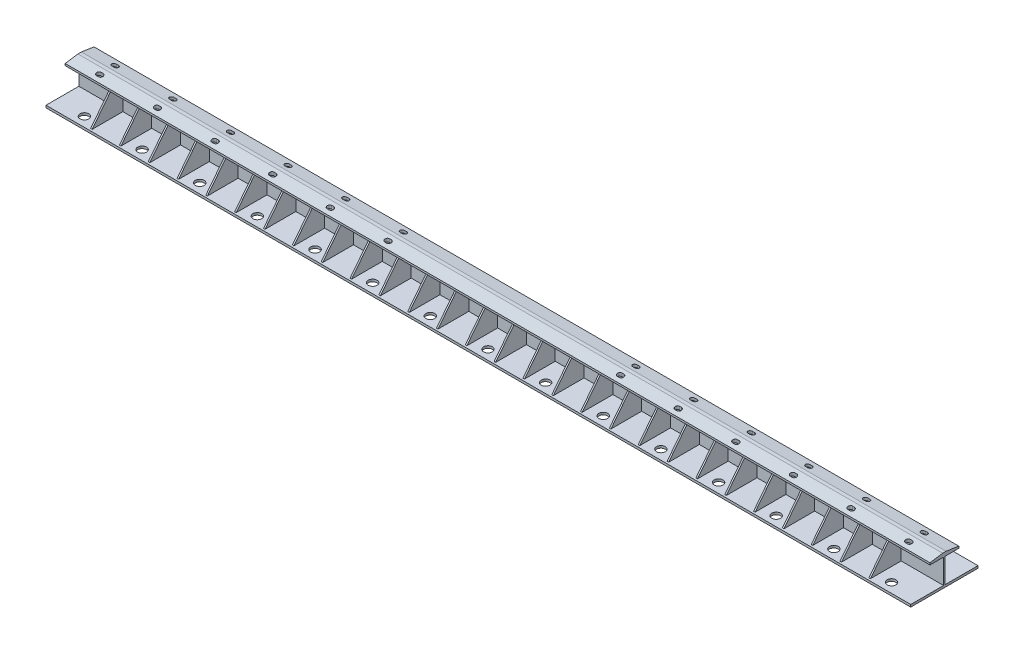
SolidWorks part; units mm, degrees
ref_plane "前视基准面" through (0, 0, 0) normal (0, 0, 1) x (1, 0, 0)
ref_plane "上视基准面" through (0, 0, 0) normal (0, 1, 0) x (1, 0, 0)
ref_plane "右视基准面" through (0, 0, 0) normal (1, 0, 0) x (0, 0, -1)
sketch "草图1" plane through (0, 0, 0) normal (0, 1, 0) x (1, 0, 0)
  line L1 (-2250, 75) -> (2250, 75)
  line L2 (-2250, 75) -> (-2250, -75)
  line L3 (-2250, -75) -> (2250, -75)
  line L4 (2250, 75) -> (2250, -75)
  line L5 (-2250, 75) -> (2250, -75) construction
  line L6 (-2250, -75) -> (2250, 75) construction
  line L24 (0, -75) -> (0, 75) construction
  line L25 (2250, 0) -> (-2250, 0) construction
extrude "凸台-拉伸1" add sketch "草图1" along normal blind 20
sketch "草图2" plane through (0, 0, 0) normal (0, -1, 0) x (1, 0, 0)
  line L0 (221, 64) -> (229, 64)
  line L1 (-2250, 4) -> (2250, 4)
  line L2 (-2250, 4) -> (-2250, -4)
  line L3 (-2250, -4) -> (2250, -4)
  line L4 (2250, 4) -> (2250, -4)
  line L5 (-2250, 4) -> (2250, -4) construction
  line L6 (-2250, -4) -> (2250, 4) construction
  line L7 (81.413, 64) -> (89.413, 64)
  line L8 (81.413, 64) -> (81.413, -64)
  line L9 (81.413, -64) -> (89.413, -64)
  line L10 (89.413, 64) -> (89.413, -64)
  line L11 (81.413, 64) -> (89.413, -64) construction
  line L12 (81.413, -64) -> (89.413, 64) construction
  line L13 (221, 64) -> (221, -64)
  line L14 (221, -64) -> (229, -64)
  line L15 (229, 64) -> (229, -64)
  line L16 (221, 64) -> (229, -64) construction
  line L17 (221, -64) -> (229, 64) construction
  line L18 (371, 64) -> (379, 64)
  line L19 (371, 64) -> (371, -64)
  line L20 (371, -64) -> (379, -64)
  line L21 (379, 64) -> (379, -64)
  line L22 (371, 64) -> (379, -64) construction
  line L23 (371, -64) -> (379, 64) construction
  line L24 (521, 64) -> (529, 64)
  line L25 (521, 64) -> (521, -64)
  line L26 (521, -64) -> (529, -64)
  line L27 (529, 64) -> (529, -64)
  line L28 (521, 64) -> (529, -64) construction
  line L29 (521, -64) -> (529, 64) construction
  line L30 (821, 64) -> (829, 64)
  line L31 (821, 64) -> (821, -64)
  line L32 (821, -64) -> (829, -64)
  line L33 (829, 64) -> (829, -64)
  line L34 (821, 64) -> (829, -64) construction
  line L35 (821, -64) -> (829, 64) construction
  line L36 (971, 64) -> (979, 64)
  line L37 (971, 64) -> (971, -64)
  line L38 (971, -64) -> (979, -64)
  line L39 (979, 64) -> (979, -64)
  line L40 (971, 64) -> (979, -64) construction
  line L41 (971, -64) -> (979, 64) construction
  line L42 (1121, 64) -> (1129, 64)
  line L43 (1121, 64) -> (1121, -64)
  line L44 (1121, -64) -> (1129, -64)
  line L45 (1129, 64) -> (1129, -64)
  line L46 (1121, 64) -> (1129, -64) construction
  line L47 (1121, -64) -> (1129, 64) construction
  line L48 (1271, 64) -> (1279, 64)
  line L49 (1271, 64) -> (1271, -64)
  line L50 (1271, -64) -> (1279, -64)
  line L51 (1279, 64) -> (1279, -64)
  line L52 (1271, 64) -> (1279, -64) construction
  line L53 (1271, -64) -> (1279, 64) construction
  line L54 (1571, 64) -> (1579, 64)
  line L55 (1571, 64) -> (1571, -64)
  line L56 (1571, -64) -> (1579, -64)
  line L57 (1579, 64) -> (1579, -64)
  line L58 (1571, 64) -> (1579, -64) construction
  line L59 (1571, -64) -> (1579, 64) construction
  line L60 (1721, 64) -> (1729, 64)
  line L61 (1721, 64) -> (1721, -64)
  line L62 (1721, -64) -> (1729, -64)
  line L63 (1729, 64) -> (1729, -64)
  line L64 (1721, 64) -> (1729, -64) construction
  line L65 (1721, -64) -> (1729, 64) construction
  line L66 (1871, 64) -> (1879, 64)
  line L67 (1871, 64) -> (1871, -64)
  line L68 (1871, -64) -> (1879, -64)
  line L69 (1879, 64) -> (1879, -64)
  line L70 (1871, 64) -> (1879, -64) construction
  line L71 (1871, -64) -> (1879, 64) construction
  line L72 (1421, 64) -> (1429, 64)
  line L73 (1421, 64) -> (1421, -64)
  line L74 (1421, -64) -> (1429, -64)
  line L75 (1429, 64) -> (1429, -64)
  line L76 (1421, 64) -> (1429, -64) construction
  line L77 (1421, -64) -> (1429, 64) construction
  line L78 (671, 64) -> (679, 64)
  line L79 (671, 64) -> (671, -64)
  line L80 (671, -64) -> (679, -64)
  line L81 (679, 64) -> (679, -64)
  line L82 (671, 64) -> (679, -64) construction
  line L83 (671, -64) -> (679, 64) construction
  line L84 (0, 75) -> (0, -75) construction
  line L85 (-2250, 75) -> (2250, 75) construction
  line L86 (2021, 64) -> (2029, 64)
  line L87 (2250, -75) -> (-2250, -75) construction
  line L88 (-2046, -64) -> (-2054, 64) construction
  line L89 (-2046, 64) -> (-2054, -64) construction
  line L90 (2046, 64) -> (2054, 64)
  line L91 (2046, 64) -> (2046, -64)
  line L92 (2046, -64) -> (2054, -64)
  line L93 (2054, 64) -> (2054, -64)
  line L94 (2046, 64) -> (2054, -64) construction
  line L95 (2046, -64) -> (2054, 64) construction
  line L96 (-671, -64) -> (-679, 64) construction
  line L97 (-671, 64) -> (-679, -64) construction
  line L98 (-1421, -64) -> (-1429, 64) construction
  line L99 (-1421, 64) -> (-1429, -64) construction
  line L100 (-1871, -64) -> (-1879, 64) construction
  line L101 (-1871, 64) -> (-1879, -64) construction
  line L102 (-1721, -64) -> (-1729, 64) construction
  line L103 (-1721, 64) -> (-1729, -64) construction
  line L104 (-1571, -64) -> (-1579, 64) construction
  line L105 (-1571, 64) -> (-1579, -64) construction
  line L106 (-1271, -64) -> (-1279, 64) construction
  line L107 (-1271, 64) -> (-1279, -64) construction
  line L108 (-1121, -64) -> (-1129, 64) construction
  line L109 (-1121, 64) -> (-1129, -64) construction
  line L110 (-971, -64) -> (-979, 64) construction
  line L111 (-971, 64) -> (-979, -64) construction
  line L112 (-821, -64) -> (-829, 64) construction
  line L113 (-821, 64) -> (-829, -64) construction
  line L114 (-521, -64) -> (-529, 64) construction
  line L115 (-521, 64) -> (-529, -64) construction
  line L116 (-371, -64) -> (-379, 64) construction
  line L117 (-371, 64) -> (-379, -64) construction
  line L118 (-221, -64) -> (-229, 64) construction
  line L119 (-221, 64) -> (-229, -64) construction
  line L120 (-81.413, -64) -> (-89.413, 64) construction
  line L121 (-81.413, 64) -> (-89.413, -64) construction
  line L122 (-2054, 64) -> (-2054, -64)
  line L123 (-2046, -64) -> (-2054, -64)
  line L124 (-2046, 64) -> (-2046, -64)
  line L125 (-2046, 64) -> (-2054, 64)
  line L126 (-679, 64) -> (-679, -64)
  line L127 (-671, -64) -> (-679, -64)
  line L128 (-671, 64) -> (-671, -64)
  line L129 (-671, 64) -> (-679, 64)
  line L130 (-1429, 64) -> (-1429, -64)
  line L131 (-1421, -64) -> (-1429, -64)
  line L132 (-1421, 64) -> (-1421, -64)
  line L133 (-1421, 64) -> (-1429, 64)
  line L134 (-1879, 64) -> (-1879, -64)
  line L135 (-1871, -64) -> (-1879, -64)
  line L136 (-1871, 64) -> (-1871, -64)
  line L137 (-1871, 64) -> (-1879, 64)
  line L138 (-1729, 64) -> (-1729, -64)
  line L139 (-1721, -64) -> (-1729, -64)
  line L140 (-1721, 64) -> (-1721, -64)
  line L141 (-1721, 64) -> (-1729, 64)
  line L142 (-1579, 64) -> (-1579, -64)
  line L143 (-1571, -64) -> (-1579, -64)
  line L144 (-1571, 64) -> (-1571, -64)
  line L145 (-1571, 64) -> (-1579, 64)
  line L146 (-1279, 64) -> (-1279, -64)
  line L147 (-1271, -64) -> (-1279, -64)
  line L148 (-1271, 64) -> (-1271, -64)
  line L149 (-1271, 64) -> (-1279, 64)
  line L150 (-1129, 64) -> (-1129, -64)
  line L151 (-1121, -64) -> (-1129, -64)
  line L152 (-1121, 64) -> (-1121, -64)
  line L153 (-1121, 64) -> (-1129, 64)
  line L154 (-979, 64) -> (-979, -64)
  line L155 (-971, -64) -> (-979, -64)
  line L156 (-971, 64) -> (-971, -64)
  line L157 (-971, 64) -> (-979, 64)
  line L158 (-829, 64) -> (-829, -64)
  line L159 (-821, -64) -> (-829, -64)
  line L160 (-821, 64) -> (-821, -64)
  line L161 (-821, 64) -> (-829, 64)
  line L162 (-529, 64) -> (-529, -64)
  line L163 (-521, -64) -> (-529, -64)
  line L164 (-521, 64) -> (-521, -64)
  line L165 (-521, 64) -> (-529, 64)
  line L166 (-379, 64) -> (-379, -64)
  line L167 (-371, -64) -> (-379, -64)
  line L168 (-371, 64) -> (-371, -64)
  line L169 (-371, 64) -> (-379, 64)
  line L170 (-229, 64) -> (-229, -64)
  line L171 (-221, -64) -> (-229, -64)
  line L172 (-221, 64) -> (-221, -64)
  line L173 (-89.413, 64) -> (-89.413, -64)
  line L174 (-81.413, -64) -> (-89.413, -64)
  line L175 (-81.413, 64) -> (-81.413, -64)
  line L176 (-81.413, 64) -> (-89.413, 64)
  line L177 (-221, 64) -> (-229, 64)
  line L178 (2021, 64) -> (2021, -64)
  line L179 (2021, -64) -> (2029, -64)
  line L180 (2029, 64) -> (2029, -64)
  line L181 (2021, 64) -> (2029, -64) construction
  line L182 (2021, -64) -> (2029, 64) construction
  line L183 (71, 64) -> (79, 64)
  line L184 (71, 64) -> (71, -64)
  line L185 (71, -64) -> (79, -64)
  line L186 (79, 64) -> (79, -64)
  line L187 (71, 64) -> (79, -64) construction
  line L188 (71, -64) -> (79, 64) construction
  line L189 (-79, 64) -> (-71, 64)
  line L190 (-79, 64) -> (-79, -64)
  line L191 (-79, -64) -> (-71, -64)
  line L192 (-71, 64) -> (-71, -64)
  line L193 (-79, 64) -> (-71, -64) construction
  line L194 (-79, -64) -> (-71, 64) construction
  line L195 (-2029, 64) -> (-2021, 64)
  line L196 (-2029, 64) -> (-2029, -64)
  line L197 (-2029, -64) -> (-2021, -64)
  line L198 (-2021, 64) -> (-2021, -64)
  line L199 (-2029, 64) -> (-2021, -64) construction
  line L200 (-2029, -64) -> (-2021, 64) construction
  point P0 (0, 0)
  point P5 (85.413, 0)
  point P10 (225, 0)
  point P15 (375, 0)
  point P20 (525, 0)
  point P25 (825, 0)
  point P30 (975, 0)
  point P35 (1125, 0)
  point P40 (1275, 0)
  point P45 (1575, 0)
  point P50 (1725, 0)
  point P55 (1875, 0)
  point P60 (1425, 0)
  point P65 (675, 0)
  point P75 (2050, 0)
  point P138 (-2050, 0)
  point P139 (-675, 0)
  point P140 (-1425, 0)
  point P141 (-1875, 0)
  point P142 (-1725, 0)
  point P143 (-1575, 0)
  point P144 (-1275, 0)
  point P145 (-1125, 0)
  point P146 (-975, 0)
  point P147 (-825, 0)
  point P148 (-525, 0)
  point P149 (-375, 0)
  point P150 (-225, 0)
  point P151 (-85.413, 0)
  point P152 (2025, 0)
  point P157 (75, 0)
  point P162 (-75, 0)
  point P167 (-2025, 0)
  dimension "D1" = 8
  dimension "D2" = 128
sketch "草图3" plane through (0, 0, 0) normal (0, -1, 0) x (1, 0, 0)
  line L0 (-610, 40) -> (-600, 40) construction
  line L1 (-610, 52) -> (-600, 52)
  line L2 (-610, 28) -> (-600, 28)
  line L3 (-910, 40) -> (-900, 40) construction
  line L4 (-910, 52) -> (-900, 52)
  line L5 (-910, 28) -> (-900, 28)
  line L6 (-1210, 40) -> (-1200, 40) construction
  line L7 (-1210, 52) -> (-1200, 52)
  line L8 (-1210, 28) -> (-1200, 28)
  line L9 (-1510, 40) -> (-1500, 40) construction
  line L10 (-1510, 52) -> (-1500, 52)
  line L11 (-1510, 28) -> (-1500, 28)
  line L12 (-1810, 40) -> (-1800, 40) construction
  line L13 (-1810, 52) -> (-1800, 52)
  line L14 (-1810, 28) -> (-1800, 28)
  line L15 (-2110, 40) -> (-2100, 40) construction
  line L16 (-2110, 52) -> (-2100, 52)
  line L17 (-2110, 28) -> (-2100, 28)
  line L18 (-2110, -40) -> (-2100, -40) construction
  line L19 (-2110, -28) -> (-2100, -28)
  line L20 (-2110, -52) -> (-2100, -52)
  line L21 (-1810, -40) -> (-1800, -40) construction
  line L22 (-1810, -28) -> (-1800, -28)
  line L23 (-1810, -52) -> (-1800, -52)
  line L24 (-1510, -40) -> (-1500, -40) construction
  line L25 (-1510, -28) -> (-1500, -28)
  line L26 (-1510, -52) -> (-1500, -52)
  line L27 (-1210, -40) -> (-1200, -40) construction
  line L28 (-1210, -28) -> (-1200, -28)
  line L29 (-1210, -52) -> (-1200, -52)
  line L30 (-910, -40) -> (-900, -40) construction
  line L31 (-910, -28) -> (-900, -28)
  line L32 (-910, -52) -> (-900, -52)
  line L33 (600, -40) -> (610, -40) construction
  line L34 (600, -28) -> (610, -28)
  line L35 (600, -52) -> (610, -52)
  line L36 (600, 40) -> (610, 40) construction
  line L37 (600, 52) -> (610, 52)
  line L38 (600, 28) -> (610, 28)
  line L39 (-610, -40) -> (-600, -40) construction
  line L40 (-610, -28) -> (-600, -28)
  line L41 (-610, -52) -> (-600, -52)
  line L42 (900, 40) -> (910, 40) construction
  line L43 (900, 52) -> (910, 52)
  line L44 (900, 28) -> (910, 28)
  line L45 (900, -40) -> (910, -40) construction
  line L46 (900, -28) -> (910, -28)
  line L47 (900, -52) -> (910, -52)
  line L48 (1200, 40) -> (1210, 40) construction
  line L49 (1200, 52) -> (1210, 52)
  line L50 (1200, 28) -> (1210, 28)
  line L51 (1200, -40) -> (1210, -40) construction
  line L52 (1200, -28) -> (1210, -28)
  line L53 (1200, -52) -> (1210, -52)
  line L54 (1500, 40) -> (1510, 40) construction
  line L55 (1500, 52) -> (1510, 52)
  line L56 (1500, 28) -> (1510, 28)
  line L57 (1500, -40) -> (1510, -40) construction
  line L58 (1500, -28) -> (1510, -28)
  line L59 (1500, -52) -> (1510, -52)
  line L60 (1800, 40) -> (1810, 40) construction
  line L61 (1800, 52) -> (1810, 52)
  line L62 (1800, 28) -> (1810, 28)
  line L63 (1800, -40) -> (1810, -40) construction
  line L64 (1800, -28) -> (1810, -28)
  line L65 (1800, -52) -> (1810, -52)
  line L66 (2100, 40) -> (2110, 40) construction
  line L67 (2100, 52) -> (2110, 52)
  line L68 (2100, 28) -> (2110, 28)
  line L69 (2100, -40) -> (2110, -40) construction
  line L70 (2100, -28) -> (2110, -28)
  line L71 (2100, -52) -> (2110, -52)
  arc A0 (-610, 52) -> (-610, 28) centre (-610, 40) ccw
  arc A1 (-600, 28) -> (-600, 52) centre (-600, 40) ccw
  arc A2 (-910, 52) -> (-910, 28) centre (-910, 40) ccw
  arc A3 (-900, 28) -> (-900, 52) centre (-900, 40) ccw
  arc A4 (-1210, 52) -> (-1210, 28) centre (-1210, 40) ccw
  arc A5 (-1200, 28) -> (-1200, 52) centre (-1200, 40) ccw
  arc A6 (-1510, 52) -> (-1510, 28) centre (-1510, 40) ccw
  arc A7 (-1500, 28) -> (-1500, 52) centre (-1500, 40) ccw
  arc A8 (-1810, 52) -> (-1810, 28) centre (-1810, 40) ccw
  arc A9 (-1800, 28) -> (-1800, 52) centre (-1800, 40) ccw
  arc A10 (-2110, 52) -> (-2110, 28) centre (-2110, 40) ccw
  arc A11 (-2100, 28) -> (-2100, 52) centre (-2100, 40) ccw
  arc A12 (-2110, -28) -> (-2110, -52) centre (-2110, -40) ccw
  arc A13 (-2100, -52) -> (-2100, -28) centre (-2100, -40) ccw
  arc A14 (-1810, -28) -> (-1810, -52) centre (-1810, -40) ccw
  arc A15 (-1800, -52) -> (-1800, -28) centre (-1800, -40) ccw
  arc A16 (-1510, -28) -> (-1510, -52) centre (-1510, -40) ccw
  arc A17 (-1500, -52) -> (-1500, -28) centre (-1500, -40) ccw
  arc A18 (-1210, -28) -> (-1210, -52) centre (-1210, -40) ccw
  arc A19 (-1200, -52) -> (-1200, -28) centre (-1200, -40) ccw
  arc A20 (-910, -28) -> (-910, -52) centre (-910, -40) ccw
  arc A21 (-900, -52) -> (-900, -28) centre (-900, -40) ccw
  arc A22 (600, -28) -> (600, -52) centre (600, -40) ccw
  arc A23 (610, -52) -> (610, -28) centre (610, -40) ccw
  arc A24 (600, 52) -> (600, 28) centre (600, 40) ccw
  arc A25 (610, 28) -> (610, 52) centre (610, 40) ccw
  arc A26 (-610, -28) -> (-610, -52) centre (-610, -40) ccw
  arc A27 (-600, -52) -> (-600, -28) centre (-600, -40) ccw
  arc A28 (900, 52) -> (900, 28) centre (900, 40) ccw
  arc A29 (910, 28) -> (910, 52) centre (910, 40) ccw
  arc A30 (900, -28) -> (900, -52) centre (900, -40) ccw
  arc A31 (910, -52) -> (910, -28) centre (910, -40) ccw
  arc A32 (1200, 52) -> (1200, 28) centre (1200, 40) ccw
  arc A33 (1210, 28) -> (1210, 52) centre (1210, 40) ccw
  arc A34 (1200, -28) -> (1200, -52) centre (1200, -40) ccw
  arc A35 (1210, -52) -> (1210, -28) centre (1210, -40) ccw
  arc A36 (1500, 52) -> (1500, 28) centre (1500, 40) ccw
  arc A37 (1510, 28) -> (1510, 52) centre (1510, 40) ccw
  arc A38 (1500, -28) -> (1500, -52) centre (1500, -40) ccw
  arc A39 (1510, -52) -> (1510, -28) centre (1510, -40) ccw
  arc A40 (1800, 52) -> (1800, 28) centre (1800, 40) ccw
  arc A41 (1810, 28) -> (1810, 52) centre (1810, 40) ccw
  arc A42 (1800, -28) -> (1800, -52) centre (1800, -40) ccw
  arc A43 (1810, -52) -> (1810, -28) centre (1810, -40) ccw
  arc A44 (2100, 52) -> (2100, 28) centre (2100, 40) ccw
  arc A45 (2110, 28) -> (2110, 52) centre (2110, 40) ccw
  arc A46 (2100, -28) -> (2100, -52) centre (2100, -40) ccw
  arc A47 (2110, -52) -> (2110, -28) centre (2110, -40) ccw
  point P2 (-605, 40)
  point P9 (-905, 40)
  point P16 (-1205, 40)
  point P23 (-1505, 40)
  point P30 (-1805, 40)
  point P37 (-2105, 40)
  point P44 (-2105, -40)
  point P51 (-1805, -40)
  point P58 (-1505, -40)
  point P65 (-1205, -40)
  point P72 (-905, -40)
  point P79 (605, -40)
  point P86 (605, 40)
  point P93 (-605, -40)
  point P100 (905, 40)
  point P107 (905, -40)
  point P114 (1205, 40)
  point P121 (1205, -40)
  point P128 (1505, 40)
  point P135 (1505, -40)
  point P142 (1805, 40)
  point P149 (1805, -40)
  point P156 (2105, 40)
  point P163 (2105, -40)
extrude "切除-拉伸1" cut sketch "草图3" against normal through all
extrude "凸台-拉伸6" add sketch "草图2" along normal blind 140 contours L1 L4 L3 L2 | L178 L179 L180 L86 | L67 L68 L69 L66 | L61 L62 L63 L60 | L55 L56 L57 L54 | L75 L74 L73 L72 | L49 L50 L51 L48 | L45 L44 L43 L42 | L37 L38 L39 L36 | L31 L32 L33 L30 | L81 L80 L79 L78 | L27 L26 L25 L24 | L19 L20 L21 L18 | L13 L14 L15 L0 | L184 L185 L186 L183 | L192 L191 L190 L189 | L172 L171 L170 L177 | L168 L167 L166 L169 | L164 L163 L162 L165 | L126 L127 L128 L129 | L158 L159 L160 L161 | L154 L155 L156 L157 | L150 L151 L152 L153 | L146 L147 L148 L149 | L130 L131 L132 L133 | L142 L143 L144 L145 | L138 L139 L140 L141 | L134 L135 L136 L137 | L196 L197 L198 L195
sketch "草图6" plane through (-2029, 0, 0) normal (-1, 0, 0) x (0, 0, 1)
  line L1 (-175, -128) -> (175, -128)
  line L2 (-175, -128) -> (-175, -140)
  line L3 (-175, -140) -> (175, -140)
  line L4 (175, -128) -> (175, -140)
  line L5 (-175, -128) -> (175, -140) construction
  line L6 (-175, -140) -> (175, -128) construction
  point P0 (0, -134)
  dimension "D1" = 12
  dimension "D2" = 350
extrude "凸台-拉伸7" add sketch "草图6" along normal blind 221 and the other way blind 4279
sketch "草图9" plane through (2250, 0, 0) normal (1, 0, 0) x (0, 0, -1)
  line L0 (-75, 10) -> (-9, 20)
  line L1 (-75, 20) -> (-75, 0) construction
  line L2 (-75, 20) -> (75, 20) construction
  line L3 (-9, 20) -> (-75, 20)
  line L4 (-75, 20) -> (-75, 10)
  line L5 (75, 10) -> (9, 20)
  line L6 (75, 20) -> (75, 0) construction
  line L7 (9, 20) -> (75, 20)
  line L8 (75, 20) -> (75, 10)
  dimension "D1" = 66
  dimension "D2" = 66
extrude "切除-拉伸2" cut sketch "草图9" against normal through all
sketch "草图13" plane through (0, 0, 64) normal (0, 0, 1) x (1, 0, 0)
  line L1 (2029, 0) -> (2021, 0)
  line L2 (2029, 0) -> (2029, -128)
  line L3 (2029, -128) -> (2021, -128)
  line L4 (2021, 0) -> (2021, -128)
extrude "凸台-拉伸8" add sketch "草图13" along normal blind 100 and the other way blind 228
sketch "草图17" plane through (0, 0, 64) normal (0, 0, 1) x (1, 0, 0)
  line L1 (1879, 0) -> (1871, 0)
  line L2 (1879, 0) -> (1879, -128)
  line L3 (1879, -128) -> (1871, -128)
  line L4 (1871, 0) -> (1871, -128)
extrude "凸台-拉伸9" add sketch "草图17" along normal blind 100 and the other way blind 220
extrude "凸台-拉伸36" add sketch "草图17<2>" along normal blind 100 and the other way blind 228
sketch "草图17<2>" plane through (0, 0, 64) normal (0, 0, 1) x (1, 0, 0) same geometry as "草图17"
sketch "草图18" plane through (0, 0, -64) normal (0, 0, -1) x (-1, 0, 0)
  line L1 (-1729, 0) -> (-1721, 0)
  line L2 (-1729, 0) -> (-1729, -128)
  line L3 (-1729, -128) -> (-1721, -128)
  line L4 (-1721, 0) -> (-1721, -128)
sketch "草图19" plane through (0, 0, -64) normal (0, 0, -1) x (-1, 0, 0)
  line L1 (-1729, 0) -> (-1721, 0)
  line L2 (-1729, 0) -> (-1729, -128)
  line L3 (-1729, -128) -> (-1721, -128)
  line L4 (-1721, 0) -> (-1721, -128)
extrude "凸台-拉伸10" add sketch "草图19" along normal blind 100 and the other way blind 228
sketch "草图20" plane through (0, 0, -64) normal (0, 0, -1) x (-1, 0, 0)
  line L1 (-1579, 0) -> (-1571, 0)
  line L2 (-1579, 0) -> (-1579, -128)
  line L3 (-1579, -128) -> (-1571, -128)
  line L4 (-1571, 0) -> (-1571, -128)
extrude "凸台-拉伸11" add sketch "草图20" along normal blind 100 and the other way blind 228
sketch "草图21" plane through (0, 0, -64) normal (0, 0, -1) x (-1, 0, 0)
  line L1 (-1429, 0) -> (-1421, 0)
  line L2 (-1429, 0) -> (-1429, -128)
  line L3 (-1429, -128) -> (-1421, -128)
  line L4 (-1421, 0) -> (-1421, -128)
extrude "凸台-拉伸12" add sketch "草图21" along normal blind 100 and the other way blind 228
sketch "草图23" plane through (0, 0, -64) normal (0, 0, -1) x (-1, 0, 0)
  line L1 (-1279, 0) -> (-1271, 0)
  line L2 (-1279, 0) -> (-1279, -128)
  line L3 (-1279, -128) -> (-1271, -128)
  line L4 (-1271, 0) -> (-1271, -128)
extrude "凸台-拉伸13" add sketch "草图23" along normal blind 100 and the other way blind 228
sketch "草图24" plane through (0, 0, -64) normal (0, 0, -1) x (-1, 0, 0)
  line L0 (-1121, -128) -> (-1121, 0) construction
  line L1 (-1129, 0) -> (-1121, 0)
  line L2 (-1129, 0) -> (-1129, -128)
  line L3 (-1129, -128) -> (-1121, -128)
  line L4 (-1121, 0) -> (-1121, -128)
  line L5 (-1121, -128) -> (-1121, 0) construction
extrude "凸台-拉伸14" add sketch "草图24" along normal blind 100 and the other way blind 228
sketch "草图25" plane through (0, 0, -64) normal (0, 0, -1) x (-1, 0, 0)
  line L1 (-979, 0) -> (-971, 0)
  line L2 (-979, 0) -> (-979, -128)
  line L3 (-979, -128) -> (-971, -128)
  line L4 (-971, 0) -> (-971, -128)
extrude "凸台-拉伸15" add sketch "草图25" along normal blind 100 and the other way blind 228
sketch "草图26" plane through (0, 0, -64) normal (0, 0, -1) x (-1, 0, 0)
  line L1 (-829, 0) -> (-821, 0)
  line L2 (-829, 0) -> (-829, -128)
  line L3 (-829, -128) -> (-821, -128)
  line L4 (-821, 0) -> (-821, -128)
extrude "凸台-拉伸16" add sketch "草图26" along normal blind 100 and the other way blind 228
sketch "草图27" plane through (0, 0, -64) normal (0, 0, -1) x (-1, 0, 0)
  line L1 (-679, 0) -> (-671, 0)
  line L2 (-679, 0) -> (-679, -128)
  line L3 (-679, -128) -> (-671, -128)
  line L4 (-671, 0) -> (-671, -128)
extrude "凸台-拉伸17" add sketch "草图27" along normal blind 100 and the other way blind 228
sketch "草图28" plane through (0, 0, -64) normal (0, 0, -1) x (-1, 0, 0)
  line L1 (-529, 0) -> (-521, 0)
  line L2 (-529, 0) -> (-529, -128)
  line L3 (-529, -128) -> (-521, -128)
  line L4 (-521, 0) -> (-521, -128)
extrude "凸台-拉伸18" add sketch "草图28" along normal blind 100 and the other way blind 228
sketch "草图29" plane through (0, 0, -64) normal (0, 0, -1) x (-1, 0, 0)
  line L1 (-379, 0) -> (-371, 0)
  line L2 (-379, 0) -> (-379, -128)
  line L3 (-379, -128) -> (-371, -128)
  line L4 (-371, 0) -> (-371, -128)
extrude "凸台-拉伸19" add sketch "草图29" along normal blind 100 and the other way blind 228
sketch "草图30" plane through (0, 0, -64) normal (0, 0, -1) x (-1, 0, 0)
  line L1 (-229, 0) -> (-221, 0)
  line L2 (-229, 0) -> (-229, -128)
  line L3 (-229, -128) -> (-221, -128)
  line L4 (-221, 0) -> (-221, -128)
extrude "凸台-拉伸20" add sketch "草图30" along normal blind 100 and the other way blind 228
sketch "草图31" plane through (0, 0, -64) normal (0, 0, -1) x (-1, 0, 0)
  line L1 (-79, 0) -> (-71, 0)
  line L2 (-79, 0) -> (-79, -128)
  line L3 (-79, -128) -> (-71, -128)
  line L4 (-71, 0) -> (-71, -128)
extrude "凸台-拉伸21" add sketch "草图31" along normal blind 100 and the other way blind 228
sketch "草图32" plane through (0, 0, -64) normal (0, 0, -1) x (-1, 0, 0)
  line L1 (71, 0) -> (79, 0)
  line L2 (71, 0) -> (71, -128)
  line L3 (71, -128) -> (79, -128)
  line L4 (79, 0) -> (79, -128)
extrude "凸台-拉伸22" add sketch "草图32" along normal blind 100 and the other way blind 228
sketch "草图33" plane through (0, 0, -64) normal (0, 0, -1) x (-1, 0, 0)
  line L1 (221, 0) -> (229, 0)
  line L2 (221, 0) -> (221, -128)
  line L3 (221, -128) -> (229, -128)
  line L4 (229, 0) -> (229, -128)
extrude "凸台-拉伸23" add sketch "草图33" along normal blind 100 and the other way blind 228
sketch "草图34" plane through (0, 0, -64) normal (0, 0, -1) x (-1, 0, 0)
  line L1 (371, 0) -> (379, 0)
  line L2 (371, 0) -> (371, -128)
  line L3 (371, -128) -> (379, -128)
  line L4 (379, 0) -> (379, -128)
extrude "凸台-拉伸24" add sketch "草图34" along normal blind 100 and the other way blind 228
sketch "草图35" plane through (0, 0, -64) normal (0, 0, -1) x (-1, 0, 0)
  line L1 (521, 0) -> (529, 0)
  line L2 (521, 0) -> (521, -128)
  line L3 (521, -128) -> (529, -128)
  line L4 (529, 0) -> (529, -128)
extrude "凸台-拉伸25" add sketch "草图35" along normal blind 100 and the other way blind 228
sketch "草图36" plane through (0, 0, -64) normal (0, 0, -1) x (-1, 0, 0)
  line L1 (671, 0) -> (679, 0)
  line L2 (671, 0) -> (671, -128)
  line L3 (671, -128) -> (679, -128)
  line L4 (679, 0) -> (679, -128)
extrude "凸台-拉伸26" add sketch "草图36" along normal blind 100 and the other way blind 228
sketch "草图37" plane through (0, 0, -64) normal (0, 0, -1) x (-1, 0, 0)
  line L1 (821, 0) -> (829, 0)
  line L2 (821, 0) -> (821, -128)
  line L3 (821, -128) -> (829, -128)
  line L4 (829, 0) -> (829, -128)
extrude "凸台-拉伸27" add sketch "草图37" along normal blind 100 and the other way blind 228
sketch "草图38" plane through (0, 0, -64) normal (0, 0, -1) x (-1, 0, 0)
  line L1 (971, 0) -> (979, 0)
  line L2 (971, 0) -> (971, -128)
  line L3 (971, -128) -> (979, -128)
  line L4 (979, 0) -> (979, -128)
extrude "凸台-拉伸28" add sketch "草图38" along normal blind 100 and the other way blind 228
sketch "草图39" plane through (0, 0, -64) normal (0, 0, -1) x (-1, 0, 0)
  line L1 (1121, 0) -> (1129, 0)
  line L2 (1121, 0) -> (1121, -128)
  line L3 (1121, -128) -> (1129, -128)
  line L4 (1129, 0) -> (1129, -128)
extrude "凸台-拉伸29" add sketch "草图39" along normal blind 100 and the other way blind 228
sketch "草图40" plane through (0, 0, -64) normal (0, 0, -1) x (-1, 0, 0)
  line L1 (1271, 0) -> (1279, 0)
  line L2 (1271, 0) -> (1271, -128)
  line L3 (1271, -128) -> (1279, -128)
  line L4 (1279, 0) -> (1279, -128)
extrude "凸台-拉伸30" add sketch "草图40" along normal blind 100 and the other way blind 228
sketch "草图41" plane through (0, 0, -64) normal (0, 0, -1) x (-1, 0, 0)
  line L1 (1421, 0) -> (1429, 0)
  line L2 (1421, 0) -> (1421, -128)
  line L3 (1421, -128) -> (1429, -128)
  line L4 (1429, 0) -> (1429, -128)
extrude "凸台-拉伸31" add sketch "草图41" along normal blind 100 and the other way blind 228
sketch "草图42" plane through (0, 0, -64) normal (0, 0, -1) x (-1, 0, 0)
  line L0 (1579, -128) -> (1571, -128) construction
  line L1 (1571, 0) -> (1579, 0)
  line L2 (1571, 0) -> (1571, -128)
  line L3 (1571, -128) -> (1579, -128)
  line L4 (1579, 0) -> (1579, -128)
  line L5 (-2250, -128) -> (2250, -128) construction
extrude "凸台-拉伸32" add sketch "草图42" along normal blind 100 and the other way blind 228
sketch "草图43" plane through (0, 0, -64) normal (0, 0, -1) x (-1, 0, 0)
  line L1 (1721, 0) -> (1729, 0)
  line L2 (1721, 0) -> (1721, -128)
  line L3 (1721, -128) -> (1729, -128)
  line L4 (1729, 0) -> (1729, -128)
extrude "凸台-拉伸33" add sketch "草图43" along normal blind 100 and the other way blind 228
sketch "草图44" plane through (0, 0, -64) normal (0, 0, -1) x (-1, 0, 0)
  line L1 (1871, 0) -> (1879, 0)
  line L2 (1871, 0) -> (1871, -128)
  line L3 (1871, -128) -> (1879, -128)
  line L4 (1879, 0) -> (1879, -128)
extrude "凸台-拉伸34" add sketch "草图44" along normal blind 100 and the other way blind 228
sketch "草图45" plane through (0, 0, -64) normal (0, 0, -1) x (-1, 0, 0)
  line L1 (2021, 0) -> (2029, 0)
  line L2 (2021, 0) -> (2021, -128)
  line L3 (2021, -128) -> (2029, -128)
  line L4 (2029, 0) -> (2029, -128)
extrude "凸台-拉伸35" add sketch "草图45" along normal blind 100 and the other way blind 228
sketch "草图46" plane through (2029, 0, 0) normal (1, 0, 0) x (0, 0, -1)
  line L0 (64, 0) -> (164, -128)
  line L1 (64, 0) -> (64, -128) construction
  line L2 (64, 0) -> (64, -128) construction
  line L3 (164, -128) -> (164, 0)
  line L4 (164, 0) -> (64, 0)
  line L5 (-64, 0) -> (-164, -128)
  line L6 (-75, 0) -> (-4, 0) construction
  line L7 (-164, -128) -> (-164, 0)
  line L8 (-164, 0) -> (-64, 0)
  dimension "D1" = 100
extrude "切除-拉伸3" cut sketch "草图46" against normal blind 4279
sketch "草图47" plane through (0, -140, 0) normal (0, -1, 0) x (1, 0, 0)
  circle A0 centre (0, 125) radius 23
  circle A1 centre (300, 125) radius 23
  circle A2 centre (600, 125) radius 23
  circle A3 centre (900, 125) radius 23
  circle A4 centre (1200, 125) radius 23
  circle A5 centre (2100, 125) radius 23
  circle A6 centre (1800, 125) radius 23
  circle A7 centre (1500, 125) radius 23
  circle A8 centre (0, -125) radius 23
  circle A9 centre (300, -125) radius 23
  circle A10 centre (600, -125) radius 23
  circle A11 centre (900, -125) radius 23
  circle A12 centre (1200, -125) radius 23
  circle A13 centre (1500, -125) radius 23
  circle A14 centre (1800, -125) radius 23
  circle A15 centre (2100, -125) radius 23
  circle A16 centre (-300, 125) radius 23
  circle A17 centre (-600, 125) radius 23
  circle A18 centre (2100, 125) radius 23
  circle A19 centre (-900, 125) radius 23
  circle A20 centre (-1200, 125) radius 23
  circle A21 centre (-1500, 125) radius 23
  circle A22 centre (-1800, 125) radius 23
  circle A23 centre (-600, -125) radius 23
  circle A24 centre (-300, -125) radius 23
  circle A25 centre (-900, -125) radius 23
  circle A26 centre (-2100, -125) radius 23
  circle A27 centre (-1800, -125) radius 23
  circle A28 centre (-1500, -125) radius 23
  circle A29 centre (-1200, -125) radius 23
  circle A30 centre (-2100, 125) radius 23
extrude "切除-拉伸4" cut sketch "草图47" against normal blind 12 contours A5 | A15 | A14 | A6 | A7 | A13 | A12 | A4 | A3 | A11 | A10 | A2 | A1 | A9 | A8 | A0 | A16 | A24 | A23 | A17 | A19 | A25 | A29 | A20 | A21 | A28 | A22 | A27 | A26 | A30
extrude "凸台-拉伸39" add sketch "草图18" against normal blind 10
sketch3d "3D草图1" plane through (0, 0, 0) normal (0, 0, 1) x (1, 0, 0)
